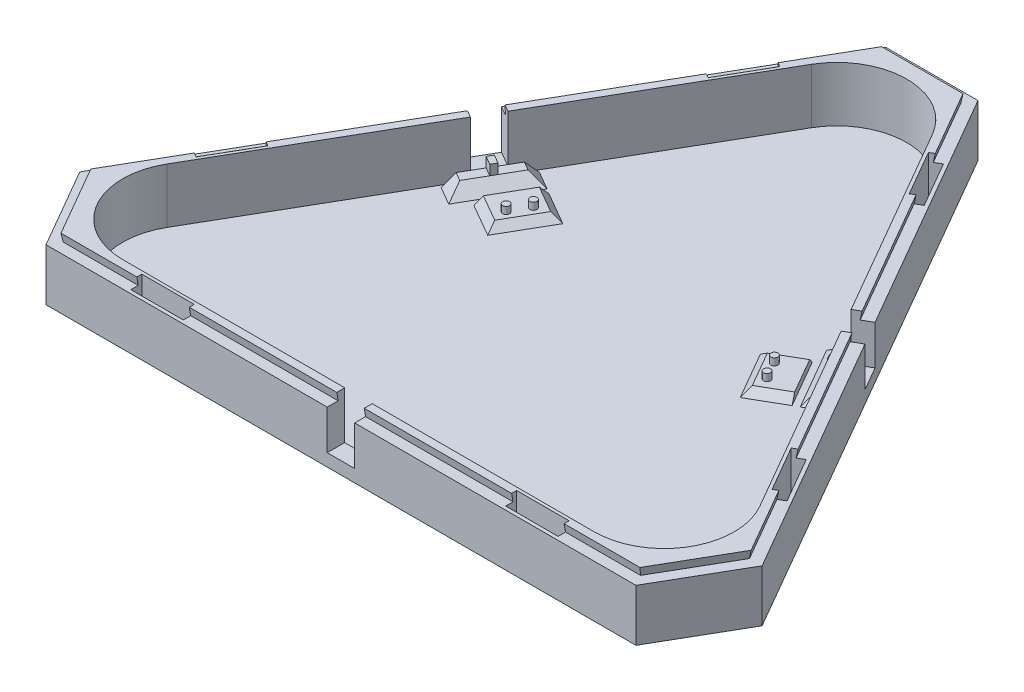
SolidWorks part; units mm, degrees
ref_plane "Plan de face" through (0, 0, 0) normal (0, 0, 1) x (1, 0, 0)
ref_plane "Plan de dessus" through (0, 0, 0) normal (0, 1, 0) x (1, 0, 0)
ref_plane "Plan de droite" through (0, 0, 0) normal (1, 0, 0) x (0, 0, -1)
sketch "Esquisse1" plane through (0, 0, 0) normal (0, 1, 0) x (1, 0, 0)
  line L3 (-77.5, -44.7446) -> (77.5, -44.7446)
  line L4 (77.5, -44.7446) -> (0, 89.4893)
  line L5 (0, 89.4893) -> (-77.5, -44.7446)
  line L6 (0, 89.4893) -> (0, -44.7446) construction
  line L7 (77.5, -44.7446) -> (-38.75, 22.3723) construction
  dimension "D1" = 155
extrude "Boss.-Extru.1" add sketch "Esquisse1" along normal blind 12 separate body
ref_axis "Axe1" through (0, -0.9, 0) along (0, 1, 0)
sketch "Esquisse2" plane through (0, 12, 0) normal (0, 1, 0) x (1, 0, 0)
  line L0 (-9.2376, 73.4893) -> (9.2376, 73.4893)
  line L1 (0, 89.4893) -> (-77.5, -44.7446) construction
  line L2 (77.5, -44.7446) -> (0, 89.4893) construction
  line L3 (9.2376, 73.4893) -> (0, 89.4893)
  line L4 (0, 89.4893) -> (-9.2376, 73.4893)
  line L5 (77.5, -44.7446) -> (68.2624, -28.7446)
  line L6 (68.2624, -28.7446) -> (59.0248, -44.7446)
  line L7 (59.0248, -44.7446) -> (77.5, -44.7446)
  line L8 (-77.5, -44.7446) -> (-59.0248, -44.7446)
  line L9 (-59.0248, -44.7446) -> (-68.2624, -28.7446)
  line L10 (-68.2624, -28.7446) -> (-77.5, -44.7446)
  point P6 (0, 73.4893)
  point P17 (0, 0)
  dimension "D1" = 16
extrude "Enlèv. mat.-Extru.1" cut sketch "Esquisse2" against normal through all
sketch "Esquisse10" plane through (0, 12, 0) normal (0, 1, 0) x (1, 0, 0)
  line L0 (-9.2376, 73.4893) -> (9.2376, 73.4893) construction
  circle A0 centre (0, 70.9893) radius 1.65
  circle A1 centre (61.4785, -35.4946) radius 1.65
  circle A2 centre (-61.4785, -35.4946) radius 1.65
  point P9 (0, 0)
  dimension "D1" = 3.3
  dimension "D2" = 2.5
  dimension "D3" = 3
extrude "Enlèv. mat.-Extru.6" [suppressed] cut sketch "Esquisse10" against normal through all
sketch "Esquisse3" plane through (0, 12, 0) normal (0, 1, 0) x (1, 0, 0)
  line L3 (12.1244, 61.4893) -> (-12.1244, 61.4893) construction
  line L4 (59.3135, -20.2446) -> (12.1244, 61.4893)
  line L5 (-12.1244, 61.4893) -> (-59.3135, -20.2446)
  line L10 (-9.2376, 73.4893) -> (9.2376, 73.4893) construction
  line L11 (-47.1891, -41.2446) -> (47.1891, -41.2446)
  line L12 (59.0132, -34.7407) -> (-47.6968, 28.0788) construction
  line L13 (0, -41.6074) -> (0, 68.4893) construction
  line L14 (47.9131, 27.5989) -> (-59.0132, -34.7407) construction
  line L15 (-9.2376, 73.4893) -> (-68.2624, -28.7446) construction
  line L16 (68.2624, -28.7446) -> (9.2376, 73.4893) construction
  line L17 (-59.0248, -44.7446) -> (59.0248, -44.7446) construction
  arc A3 (12.1244, 61.4893) -> (-12.1244, 61.4893) centre (0, 54.4893) ccw
  arc A4 (47.1891, -41.2446) -> (59.3135, -20.2446) centre (47.1891, -27.2446) ccw
  arc A5 (-59.3135, -20.2446) -> (-47.1891, -41.2446) centre (-47.1891, -27.2446) ccw
  point P23 (0, 0)
  dimension "D2" = 14
  dimension "D1" = 3.5
  dimension "D4" = 3.5
  dimension "D5" = 3.5
  dimension "D3" = 3
extrude "Enlèv. mat.-Extru.2" cut sketch "Esquisse3" against normal blind 11
sketch "Esquisse4" plane through (0, 12, 0) normal (0, 1, 0) x (1, 0, 0)
  line L0 (37.0939, 18.2408) -> (34.3439, 23.0039)
  line L1 (59.3135, -20.2446) -> (12.1244, 61.4893) construction
  line L2 (34.3439, 23.0039) -> (37.375, 24.7539)
  line L3 (68.2624, -28.7446) -> (9.2376, 73.4893) construction
  line L4 (37.375, 24.7539) -> (40.125, 19.9908)
  line L5 (40.125, 19.9908) -> (37.0939, 18.2408)
  line L14 (-2.75, -44.7446) -> (-2.75, -41.2446)
  line L15 (-2.75, -41.2446) -> (2.75, -41.2446)
  line L16 (2.75, -41.2446) -> (2.75, -44.7446)
  line L17 (2.75, -44.7446) -> (-2.75, -44.7446)
  line L18 (-37.375, 24.7539) -> (-34.3439, 23.0039)
  line L19 (-34.3439, 23.0039) -> (-37.0939, 18.2408)
  line L20 (-37.0939, 18.2408) -> (-40.125, 19.9908)
  line L21 (-40.125, 19.9908) -> (-37.375, 24.7539)
  point P9 (38.75, 22.3723)
  point P10 (38.75, 22.3723)
  point P21 (0, 0)
  dimension "D1" = 5.5
  dimension "D2" = 3
extrude "Enlèv. mat.-Extru.3" cut sketch "Esquisse4" against normal blind 9.5
sketch "Esquisse5" plane through (0, 1, 0) normal (0, 1, 0) x (1, 0, 0)
  line L0 (27.3541, 18.9106) -> (30.0541, 14.2341)
  line L2 (28.8221, 12.368) -> (25.1221, 18.7766)
  line L4 (40.125, 19.9908) -> (37.375, 24.7539) construction
  line L5 (59.3135, -20.2446) -> (12.1244, 61.4893) construction
  line L6 (28.7041, 16.5723) -> (38.75, 22.3723) construction
  line L7 (27.3541, 18.9106) -> (29.9522, 20.4106)
  line L8 (29.9522, 20.4106) -> (29.4522, 21.2766)
  line L9 (29.4522, 21.2766) -> (25.1221, 18.7766)
  line L11 (33.1522, 14.868) -> (28.8221, 12.368)
  line L12 (32.6522, 15.7341) -> (33.1522, 14.868)
  line L13 (30.0541, 14.2341) -> (32.6522, 15.7341)
  dimension "D1" = 8.1
  dimension "D2" = 1
  dimension "D3" = 2.7
  dimension "D4" = 2
  dimension "D5" = 5
ref_plane "Plan2" through (0, 0, 0) normal (-1, 0, 0) x (0, 0, 1)
ref_plane "Plan3" through (0, 0, 0) normal (-0.5, 0, 0.866) x (0.866, 0, 0.5)
ref_plane "Plan4" through (0, 0, 0) normal (0.5, 0, 0.866) x (0.866, 0, -0.5)
sketch "Esquisse11" plane through (0, 0, 41.2446) normal (0, 0, -1) x (-1, 0, 0)
  line L0 (47.1891, 1) -> (-47.1891, 1) construction
  line L2 (-47.1891, 1) -> (-47.1891, 12) construction
  line L3 (0, 0) -> (0, 20.2129) construction
  circle A0 centre (-32.1891, 6.5) radius 5.15
  circle A1 centre (32.1891, 6.5) radius 5.15
  dimension "D1" = 10.3
  dimension "D3" = 15
  dimension "D2" = 5.5
extrude "Enlèv. mat.-Extru.7" [suppressed] cut sketch "Esquisse11" against normal blind 2
pattern_circular "Répétition circulaire1" [suppressed] count 3 over 360 about axis through (0, -0.9, 0) along (0, 1, 0) of bodies 123
chamfer "Chanfrein1" [suppressed] distance 0.4 angle 45
ref_plane "Plan5" through (0, 6.5, 0) normal (0, 1, 0) x (1, 0, 0)
sketch "Esquisse12" plane through (0, 1, 0) normal (0, 1, 0) x (1, 0, 0)
  line L0 (23.9284, 16.6441) -> (28.0284, 9.5427)
  line L1 (23.9284, 16.6441) -> (29.2978, 19.7441)
  line L2 (28.0284, 9.5427) -> (33.3978, 12.6427)
  line L3 (29.2978, 19.7441) -> (33.3978, 12.6427)
  line L4 (59.3135, -20.2446) -> (12.1244, 61.4893) construction
  line L6 (37.0939, 18.2408) -> (40.125, 19.9908) construction
  dimension "D1" = 8.2
  dimension "D2" = 6.2
  dimension "D3" = 6
  dimension "D4" = 3
extrude "Boss.-Extru.2" add sketch "Esquisse12" along normal blind 1.4
sketch "Esquisse13" plane through (0, 2.4, 0) normal (0, 1, 0) x (1, 0, 0)
  line L0 (26.364, 15.6254) -> (28.364, 12.1613) construction
  line L1 (33.3978, 12.6427) -> (29.2978, 19.7441) construction
  line L2 (27.364, 13.8934) -> (31.3478, 16.1934) construction
  line L3 (23.9284, 16.6441) -> (28.0284, 9.5427) construction
  circle A0 centre (26.364, 15.6254) radius 0.7
  circle A1 centre (28.364, 12.1613) radius 0.7
  dimension "D1" = 1.4
  dimension "D2" = 4
  dimension "D3" = 1.6
extrude "Boss.-Extru.3" add sketch "Esquisse13" along normal blind 1.4
sketch "Esquisse14" plane through (0, 1, 0) normal (0, 1, 0) x (1, 0, 0)
  line L4 (34.3439, 23.0039) -> (37.0939, 18.2408) construction
  line L5 (35.7189, 20.6223) -> (35.1993, 20.3223) construction
  line L6 (59.3135, -20.2446) -> (12.1244, 61.4893) construction
  line L7 (32.6993, 24.6524) -> (37.6993, 15.9922)
  line L8 (32.6993, 24.6524) -> (30.9672, 23.6524)
  line L9 (37.6993, 15.9922) -> (35.9672, 14.9922)
  line L10 (30.9672, 23.6524) -> (35.9672, 14.9922)
  line L11 (59.3135, -20.2446) -> (12.1244, 61.4893) construction
  dimension "D1" = 10
  dimension "D2" = 2
  dimension "D3" = 0.6
extrude "Boss.-Extru.6" add sketch "Esquisse14" along normal blind 2.2
sketch "Esquisse15" plane through (0, 3.2, 0) normal (0, 1, 0) x (1, 0, 0)
  line L0 (34.8993, 20.8419) -> (35.4993, 19.8027)
  line L1 (34.8993, 20.8419) -> (33.1672, 19.8419)
  line L2 (35.4993, 19.8027) -> (33.7672, 18.8027)
  line L3 (33.1672, 19.8419) -> (33.7672, 18.8027)
  line L4 (37.6993, 15.9922) -> (32.6993, 24.6524) construction
  line L5 (30.9672, 23.6524) -> (35.9672, 14.9922) construction
  line L6 (37.6993, 15.9922) -> (32.6993, 24.6524) construction
  point P11 (35.1993, 20.3223)
  point P12 (35.1993, 20.3223)
  dimension "D1" = 1.2
extrude "Boss.-Extru.7" add sketch "Esquisse15" along normal blind 2
chamfer "Chanfrein3" distance 2.2 angle 45 3 edges at (33.4672, 1, -19.3223) (36.8333, 1, -15.4922) (31.8333, 1, -24.1524)
chamfer "Chanfrein4" distance 1.4 angle 45 3 edges at (26.6131, 1, -18.1941) (25.9784, 1, -13.0934) (30.7131, 1, -11.0927)
pattern_circular "Répétition circulaire2" count 2 over 120 about axis through (0, -0.9, 0) along (0, 1, 0) of "Boss.-Extru.2", "Boss.-Extru.3", "Boss.-Extru.6", "Boss.-Extru.7", "Chanfrein3", "Chanfrein4"
sketch "Esquisse16" plane through (0, 0, 0) normal (0, 1, 0) x (1, 0, 0)
  line L0 (11.2217, 27.4997) -> (41.3465, -26.6864)
  line L1 (-19.3685, 82.5231) -> (-119.2403, 26.9993)
  line L2 (72.2349, -82.2461) -> (-27.6369, -137.7698)
  line L3 (-119.2403, 26.9993) -> (-27.6369, -137.7698)
  line L4 (-19.3685, 82.5231) -> (51.5403, 121.9449)
  line L6 (51.5403, 121.9449) -> (82.1306, 66.9215)
  line L7 (11.2217, 27.4997) -> (82.1306, 66.9215)
  line L8 (72.2349, -82.2461) -> (117.9546, -56.8282)
  line L10 (117.9546, -56.8282) -> (87.0662, -1.2686)
  line L11 (41.3465, -26.6864) -> (87.0662, -1.2686)
extrude "Enlèv. mat.-Extru.9" [suppressed] cut sketch "Esquisse16" along normal through all
sketch "Esquisse17" plane through (0, 12, 0) normal (0, 1, 0) x (1, 0, 0)
  line L0 (37.375, 24.7539) -> (9.2376, 73.4893) construction
  line L1 (-9.2376, 73.4893) -> (9.2376, 73.4893) construction
  line L2 (-9.2376, 73.4893) -> (-37.375, 24.7539) construction
  line L3 (-40.125, 19.9908) -> (-68.2624, -28.7446) construction
  line L4 (-59.0248, -44.7446) -> (-68.2624, -28.7446) construction
  line L5 (-59.0248, -44.7446) -> (-2.75, -44.7446) construction
  line L6 (2.75, -44.7446) -> (59.0248, -44.7446) construction
  line L7 (68.2624, -28.7446) -> (59.0248, -44.7446) construction
  line L8 (68.2624, -28.7446) -> (40.125, 19.9908) construction
  line L9 (37.375, 24.7539) -> (9.2376, 73.4893)
  line L10 (-9.2376, 73.4893) -> (9.2376, 73.4893)
  line L11 (-9.2376, 73.4893) -> (-37.375, 24.7539)
  line L12 (-40.125, 19.9908) -> (-68.2624, -28.7446)
  line L13 (-59.0248, -44.7446) -> (-68.2624, -28.7446)
  line L14 (-59.0248, -44.7446) -> (-2.75, -44.7446)
  line L15 (2.75, -44.7446) -> (59.0248, -44.7446)
  line L16 (68.2624, -28.7446) -> (59.0248, -44.7446)
  line L17 (68.2624, -28.7446) -> (40.125, 19.9908)
extrude "Enlèv. de mat.-Extru.-Mince1" cut sketch "Esquisse17" against normal blind 1.6 draft 10 thin draft outward yes thin type one direction reverse wall 1.9
sketch "Esquisse18" plane through (0, 12, 0) normal (0, 1, 0) x (1, 0, 0)
  line L1 (32.25, -41.8446) -> (42.75, -41.8446)
  line L2 (32.25, -41.8446) -> (32.25, -44.0446)
  line L3 (32.25, -44.0446) -> (42.75, -44.0446)
  line L4 (42.75, -41.8446) -> (42.75, -44.0446)
  line L5 (59.0248, -44.7446) -> (2.75, -44.7446) construction
  line L6 (2.75, -41.2446) -> (47.1891, -41.2446) construction
  line L7 (0, -44.7446) -> (0, -27.4415) construction
  line L8 (-2.75, -44.7446) -> (2.75, -44.7446) construction
  line L9 (-32.25, -41.8446) -> (-32.25, -44.0446)
  line L10 (-32.25, -41.8446) -> (-42.75, -41.8446)
  line L11 (-42.75, -41.8446) -> (-42.75, -44.0446)
  line L12 (-32.25, -44.0446) -> (-42.75, -44.0446)
  line L13 (-52.3635, -7.007) -> (-57.6135, -16.1003)
  line L14 (-52.3635, -7.007) -> (-54.2688, -5.907)
  line L15 (-54.2688, -5.907) -> (-59.5188, -15.0003)
  line L16 (-57.6135, -16.1003) -> (-59.5188, -15.0003)
  line L17 (-20.1135, 48.8516) -> (-22.0188, 49.9516)
  line L18 (-20.1135, 48.8516) -> (-14.8635, 57.9449)
  line L19 (-14.8635, 57.9449) -> (-16.7688, 59.0449)
  line L20 (-22.0188, 49.9516) -> (-16.7688, 59.0449)
  line L22 (20.1135, 48.8516) -> (14.8635, 57.9449)
  line L23 (20.1135, 48.8516) -> (22.0188, 49.9516)
  line L24 (22.0188, 49.9516) -> (16.7688, 59.0449)
  line L25 (14.8635, 57.9449) -> (16.7688, 59.0449)
  line L26 (52.3635, -7.007) -> (54.2688, -5.907)
  line L27 (52.3635, -7.007) -> (57.6135, -16.1003)
  line L28 (57.6135, -16.1003) -> (59.5188, -15.0003)
  line L29 (54.2688, -5.907) -> (59.5188, -15.0003)
  line L31 (-38.75, 22.3723) -> (-23.765, 13.7208) construction
  line L32 (38.75, 22.3723) -> (23.765, 13.7208) construction
  point P4 (37.5, -44.0446)
  point P18 (5.5874, -4.2167)
  point P41 (0, 0)
  dimension "D1" = 2.2
  dimension "D2" = 0.7
  dimension "D3" = 0.6
  dimension "D4" = 75
  dimension "D5" = 10.5
  dimension "D6" = 3
extrude "Enlèv. mat.-Extru.10" cut sketch "Esquisse18" against normal up to surface (11 mm away) up to face at (0, 1, 0)
equation "\"D5@Esquisse3\"=\"D1@Esquisse3\""
equation "\"D4@Esquisse3\"=\"D1@Esquisse3\""
